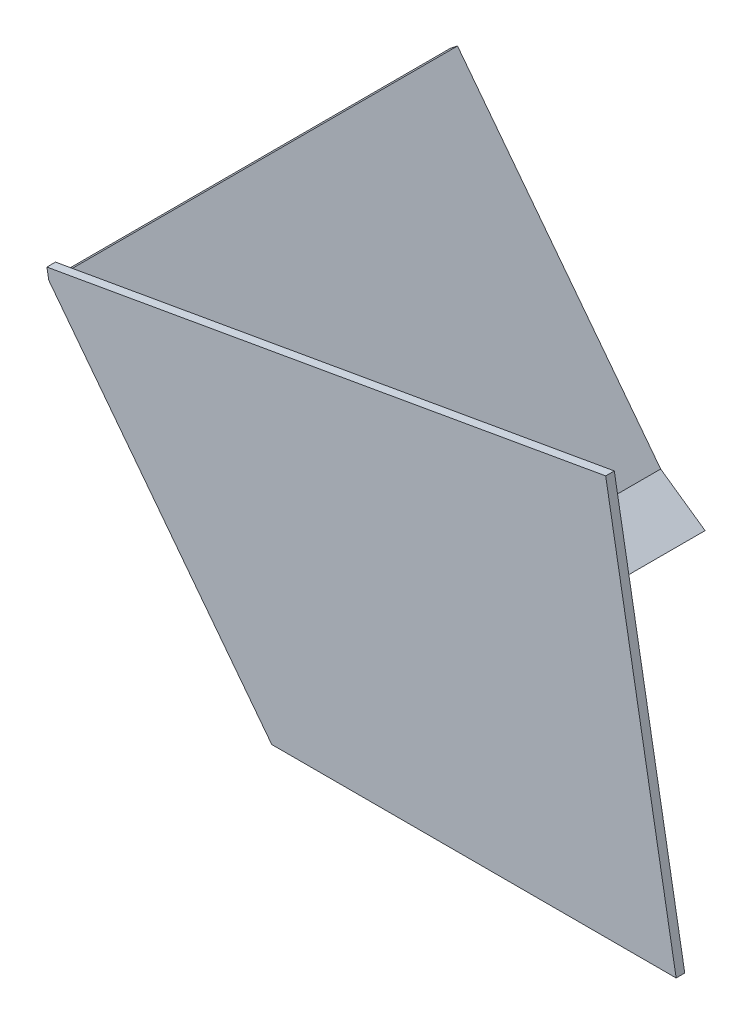
SolidWorks part; units mm, degrees
ref_plane "Front Plane" through (0, 0, 0) normal (0, 0, 1) x (1, 0, 0)
ref_plane "Top Plane" through (0, 0, 0) normal (0, 1, 0) x (1, 0, 0)
ref_plane "Right Plane" through (0, 0, 0) normal (1, 0, 0) x (0, 0, -1)
ref_axis "Axis1" through (0, 0, -14.8175) along (0, 0, 1)
sketch "Sketch1" plane through (0, 0, 0) normal (0, 0, 1) x (1, 0, 0)
  line L0 (-145.0806, 0) -> (145.0806, 0) construction
  line L1 (-162.6855, 22.9431) -> (-312.49, 218.1722)
  line L4 (-153.0846, 0) -> (-317.5278, 214.3065)
  line L5 (-317.5278, 214.3065) -> (-312.49, 218.1722)
  line L9 (-129.9194, 0) -> (-162.6855, 22.9431)
  line L10 (-129.9194, 0) -> (-153.0846, 0)
  line L11 (-162.6855, 22.9431) -> (-145.0806, 0) construction
  line L12 (145.0806, 0) -> (272.0615, 243.928) construction
  point P4 (0, 0)
  dimension "D1" = 52.5
  dimension "D2" = 35
  dimension "D3" = 275
  dimension "D4" = 275
  dimension "D5" = 40
  dimension "D6" = 6.35
  dimension "D7" = 62.5
  dimension "D8" = 275
extrude "Boss-Extrude1" add sketch "Sketch1" along normal blind 290
sketch "Sketch2" plane through (0, 0, 290) normal (0, 0, 1) x (1, 0, 0)
  line L0 (-153.0846, 0) -> (-317.5278, 214.3065)
  line L1 (-318.8842, 221.999) -> (93.1263, 294.6476)
  line L3 (145.0806, 0) -> (-153.0846, 0)
  line L4 (-317.5278, 214.3065) -> (-153.0846, 0) construction
  line L7 (-317.5278, 214.3065) -> (-318.8842, 221.999)
  line L8 (-312.49, 218.1722) -> (-317.5278, 214.3065) construction
  line L10 (145.0806, 0) -> (93.1263, 294.6476)
  line L11 (-153.0846, 0) -> (-129.9194, 0) construction
  point P2 (0, 0)
  dimension "D1" = 10
  dimension "D2" = 274
  dimension "D3" = 275
extrude "Boss-Extrude2" add sketch "Sketch2" along normal blind 6.35
ref_plane "Plane1" through (0, 0, 0) normal (0.9848, 0.1736, 0) x (0, 0, 1)
